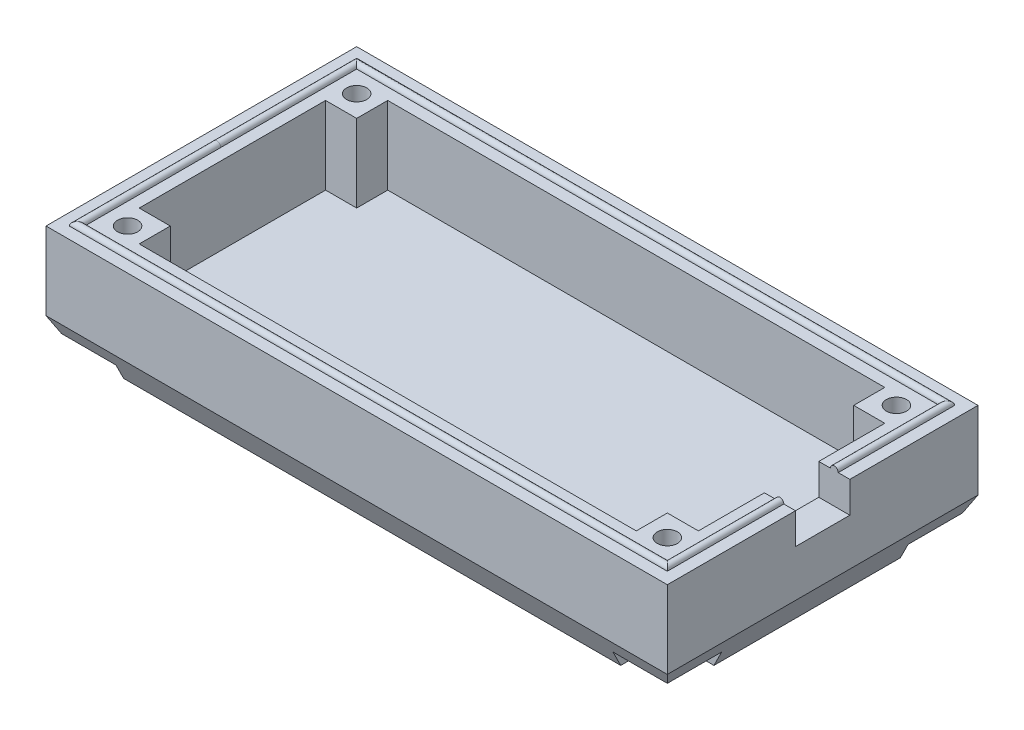
SolidWorks part; units mm, degrees
ref_plane "Piano frontale" through (0, 0, 0) normal (0, 0, 1) x (1, 0, 0)
ref_plane "Piano superiore" through (0, 0, 0) normal (0, 1, 0) x (1, 0, 0)
ref_plane "Piano destro" through (0, 0, 0) normal (1, 0, 0) x (0, 0, -1)
sketch "Schizzo1" plane through (0, 0, 0) normal (0, 1, 0) x (1, 0, 0)
  line L1 (20, -10) -> (-20, -10)
  line L2 (20, -10) -> (20, 10)
  line L3 (20, 10) -> (-20, 10)
  line L4 (-20, -10) -> (-20, 10)
  line L5 (20, -10) -> (-20, 10) construction
  line L6 (20, 10) -> (-20, -10) construction
  point P0 (0, 0)
  dimension "D1" = 40
  dimension "D2" = 20
extrude "Estrusione-Estrusione1" add sketch "Schizzo1" against normal blind 7
sketch "Schizzo2" plane through (0, 0, 0) normal (0, 1, 0) x (1, 0, 0)
  line L0 (20, 10) -> (-20, 10) construction
  line L1 (-16, 8) -> (16, 8)
  line L2 (-18, 6) -> (-18, -6)
  line L3 (-16, -8) -> (16, -8)
  line L4 (18, 6) -> (18, -6)
  line L7 (-18, 6) -> (-16, 6)
  line L8 (-20, 10) -> (-20, -10) construction
  line L9 (-16, 6) -> (-16, 8)
  line L10 (16, -8) -> (16, -6)
  line L11 (16, -6) -> (18, -6)
  line L12 (18, 6) -> (16, 6)
  line L13 (16, 6) -> (16, 8)
  line L14 (-16, -8) -> (-16, -6)
  line L15 (-16, -6) -> (-18, -6)
  point P0 (0, 0)
  dimension "D1" = 2
  dimension "D2" = 2
  dimension "D3" = 2
  dimension "D4" = 12
  dimension "D5" = 32
extrude "Taglio-Estrusione1" cut sketch "Schizzo2" against normal blind 5
sketch "Schizzo3" plane through (0, 0, 0) normal (0, 0, 1) x (1, 0, 0)
  line L0 (-20, 0) -> (20, 0) construction
  line L1 (-18.75, 0) -> (-19.25, 0)
  arc A0 (-18.75, 0) -> (-19.25, 0) centre (-19, 0) ccw
  dimension "D2" = 0.5
  dimension "D1" = 1
sketch "Schizzo4" plane through (0, 0, 0) normal (0, 1, 0) x (1, 0, 0)
  line L0 (-20, 10) -> (-20, -10) construction
  line L1 (19, -9) -> (-19, -9)
  line L2 (19, -9) -> (19, 9)
  line L3 (19, 9) -> (-19, 9)
  line L4 (-19, -9) -> (-19, 9)
  line L5 (19, -9) -> (-19, 9) construction
  line L6 (19, 9) -> (-19, -9) construction
  line L7 (20, 10) -> (-20, 10) construction
  point P0 (0, 0)
  dimension "D1" = 1
  dimension "D2" = 1
sweep "Sweep1" add profiles "Schizzo3" path "Schizzo4"
chamfer "Smusso1" distance 1 distance2 2 4 edges at (0, -7, 10) (20, -7, 0) (0, -7, -10) (-20, -7, 0) first distance on face at (0, -7, 0)
sketch "Schizzo5" plane through (0, -7, 0) normal (0, -1, 0) x (1, 0, 0)
  line L1 (-20, 10) -> (-16, 10)
  line L2 (-20, 10) -> (-20, 6)
  line L3 (-20, 6) -> (-16, 6)
  line L4 (-16, 10) -> (-16, 6)
  line L5 (20, 10) -> (16, 10)
  line L6 (20, 10) -> (20, 6)
  line L7 (20, 6) -> (16, 6)
  line L8 (16, 10) -> (16, 6)
  line L9 (20, -10) -> (16, -10)
  line L10 (20, -10) -> (20, -6)
  line L11 (20, -6) -> (16, -6)
  line L12 (16, -10) -> (16, -6)
  line L13 (-20, -10) -> (-16, -10)
  line L14 (-20, -10) -> (-20, -6)
  line L15 (-20, -6) -> (-16, -6)
  line L16 (-16, -10) -> (-16, -6)
  dimension "D1" = 4
extrude "Taglio-Estrusione2" cut sketch "Schizzo5" against normal blind 1
hole_wizard "Foro per Vite M1-1" positions "Schizzo6" profile "Schizzo7" hole size "M1" standard "ISO" end condition through all
sketch "Schizzo6" plane through (0, -6, 0) normal (0, -1, 0) x (-1, 0, 0)
  line L0 (-20, -10) -> (-20, 10) construction
  line L2 (-20, 10) -> (20, 10) construction
  point P0 (-17.375, 7.375)
  dimension "D1" = 2.625
  dimension "D2" = 2.625
sketch "Schizzo7" plane through (17.375, -6, -7.375) normal (1, 0, 0) x (0, 0, -1)
  line L0 (0, 0) -> (0, 6.25)
  line L1 (0, 6.25) -> (0.65, 6.25)
  line L2 (0.65, 6.25) -> (0.65, 0.025)
  line L3 (0.65, 0.025) -> (0.675, 0)
  line L5 (0.675, 0) -> (0, 0)
  line L6 (-0.65, 0.025) -> (-0.675, 0) construction
  line L11 (0, -6.35) -> (0, 107.95) construction
  dimension "Thru Hole Dia." = 1.3
  dimension "Thru Hole Depth" = 6.25
  dimension "Near C'Sink Dia." = 1.35
  dimension "Near C'Sink Angle" = 90
cosmetic thread "Cosmetic Thread1" parameters "D2"=2.3
mirror "Specchia1" about plane through (0, 0, 0) normal (1, 0, 0) of "Foro per Vite M1-1"
cosmetic thread "Cosmetic Thread2" parameters "D2"=2.3
mirror "Specchia2" about plane through (0, 0, 0) normal (0, 0, 1) of "Specchia1"
cosmetic thread "Cosmetic Thread3" parameters "D2"=2.3
cosmetic thread "Cosmetic Thread4" parameters "D2"=2.3
sketch "Schizzo8" plane through (20, 0, 0) normal (1, 0, 0) x (0, 0, -1)
  line L1 (-1.75, 2) -> (1.75, 2)
  line L2 (-1.75, 2) -> (-1.75, -2)
  line L3 (-1.75, -2) -> (1.75, -2)
  line L4 (1.75, 2) -> (1.75, -2)
  line L5 (-1.75, 2) -> (1.75, -2) construction
  line L6 (-1.75, -2) -> (1.75, 2) construction
  point P0 (0, 0)
  dimension "D1" = 2
  dimension "D2" = 3.5
extrude "Taglio-Estrusione3" cut sketch "Schizzo8" against normal blind 3 and the other way through all
